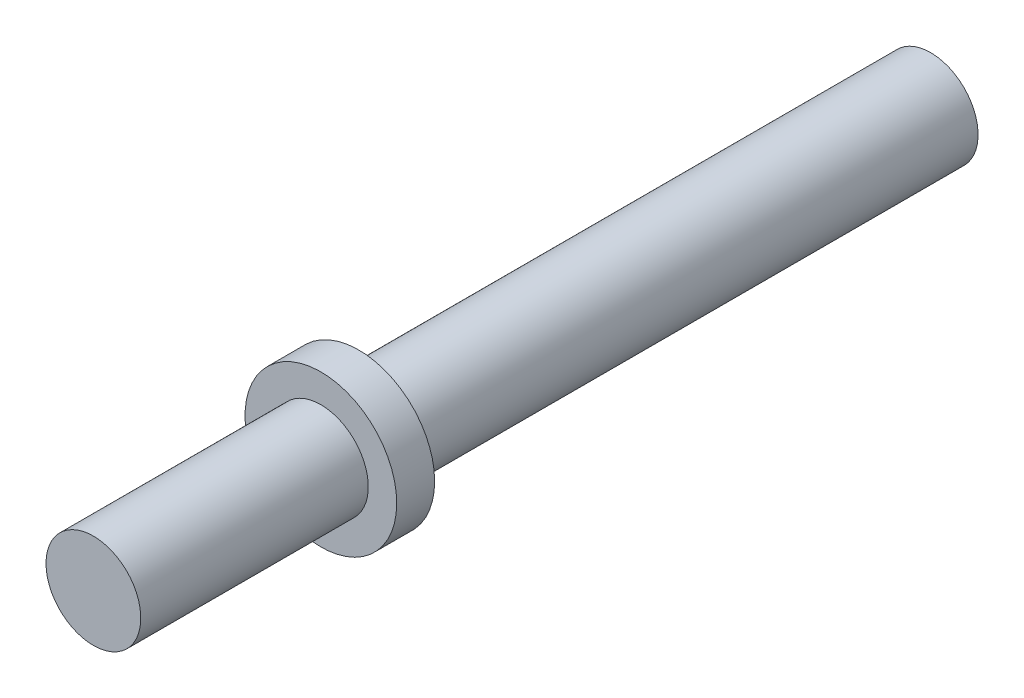
SolidWorks part; units mm, degrees
material "PVC Rigid"
ref_plane "Front Plane" through (0, 0, 0) normal (0, 0, 1) x (1, 0, 0)
ref_plane "Top Plane" through (0, 0, 0) normal (0, 1, 0) x (1, 0, 0)
ref_plane "Right Plane" through (0, 0, 0) normal (1, 0, 0) x (0, 0, -1)
sketch "Sketch1" plane through (0, 0, 0) normal (0, 0, 1) x (1, 0, 0)
  circle A0 centre (-32.0187, -41.7454) radius 1.5
extrude "Plunger_stem" add sketch "Sketch1" along normal blind 26.4999 from offset 17.5001
sketch "Sketch2" plane through (0, 0, 0) normal (0, 0, 1) x (1, 0, 0)
  circle A0 centre (-32.0187, -41.7454) radius 2.4
extrude "Captive_shoulder" add sketch "Sketch2" along normal blind 1.2 from offset 35.6
sketch "Sketch3" plane through (0, 0, 0) normal (0, 0, 1) x (1, 0, 0)
  circle A0 centre (-32.0187, -41.7454) radius 2.8
extrude "Finger_button_cap_D5p6" [suppressed] add sketch "Sketch3" along normal blind 1.2 from offset 42.8
